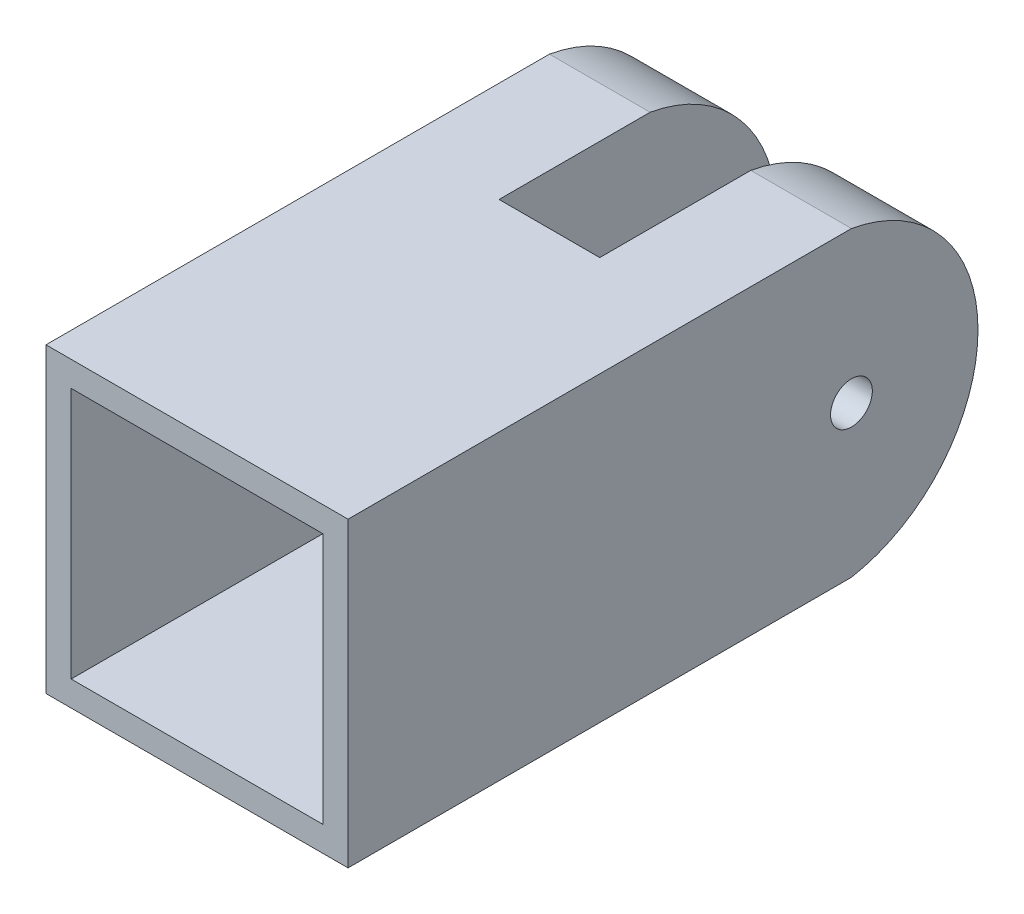
SolidWorks part; units mm, degrees
ref_plane "Front Plane" through (0, 0, 0) normal (0, 0, 1) x (1, 0, 0)
ref_plane "Top Plane" through (0, 0, 0) normal (0, 1, 0) x (1, 0, 0)
ref_plane "Right Plane" through (0, 0, 0) normal (1, 0, 0) x (0, 0, -1)
sketch "Sketch2" plane through (0, 0, 0) normal (0, 0, 1) x (1, 0, 0)
  line L1 (-30, 30) -> (30, 30)
  line L2 (-30, 30) -> (-30, -30)
  line L3 (-30, -30) -> (30, -30)
  line L4 (30, 30) -> (30, -30)
  line L5 (-30, 30) -> (30, -30) construction
  line L6 (-30, -30) -> (30, 30) construction
  point P0 (0, 0)
  dimension "D1" = 60
  dimension "D2" = 60
extrude "Boss-Extrude1" add sketch "Sketch2" along normal blind 70
ref_plane "Plane1" through (0, 0, 0) normal (0, 0, -1) x (-1, 0, 0)
sketch "Sketch3" plane through (0, 0, 0) normal (0, 0, -1) x (-1, 0, 0)
  line L0 (-30, 30) -> (30, 30) construction
  line L1 (30, -30) -> (10, -30)
  line L2 (30, -30) -> (30, 30)
  line L3 (30, 30) -> (10, 30)
  line L4 (10, -30) -> (10, 30)
  line L6 (-30, -30) -> (-10, -30)
  line L7 (-30, -30) -> (-30, 30)
  line L8 (-30, 30) -> (-10, 30)
  line L9 (-10, -30) -> (-10, 30)
  dimension "D1" = 20
  dimension "D2" = 20
extrude "Boss-Extrude2" add sketch "Sketch3" along normal blind 30
ref_plane "Plane2" through (-30, 0, 0) normal (-1, 0, 0) x (0, 0, 1)
sketch "Sketch4" plane through (-30, 0, 0) normal (-1, 0, 0) x (0, 0, 1)
  line L0 (-30, -30) -> (-30, 30)
  arc A0 (-30, -30) -> (-30, 30) centre (-24.6689, 0) cw
  dimension "D1" = 30.47
extrude "Boss-Extrude3" add sketch "Sketch4" against normal blind 20
ref_plane "Plane3" through (30, 0, 0) normal (1, 0, 0) x (0, 0, -1)
sketch "Sketch5" plane through (30, 0, 0) normal (1, 0, 0) x (0, 0, -1)
  line L0 (30, 30) -> (30, -30)
  arc A0 (30, 30) -> (30, -30) centre (24.6689, 0) cw
  dimension "D1" = 30.47
extrude "Boss-Extrude4" add sketch "Sketch5" against normal blind 20
ref_plane "Plane4" through (0, 0, 70) normal (0, 0, 1) x (1, 0, 0)
sketch "Sketch6" plane through (0, 0, 70) normal (0, 0, 1) x (1, 0, 0)
  line L0 (30, 30) -> (-30, 30) construction
  line L1 (-25, 25) -> (25, 25)
  line L2 (-25, 25) -> (-25, -25)
  line L3 (-25, -25) -> (25, -25)
  line L4 (25, 25) -> (25, -25)
  line L5 (-25, 25) -> (25, -25) construction
  line L6 (-25, -25) -> (25, 25) construction
  line L7 (30, -30) -> (30, 30) construction
  point P0 (0, 0)
  dimension "D1" = 5
  dimension "D2" = 5
extrude "Cut-Extrude1" cut sketch "Sketch6" against normal blind 67
ref_plane "Plane5" through (10, 0, 0) normal (-1, 0, 0) x (0, 0, 1)
sketch "Sketch7" plane through (10, 0, 0) normal (-1, 0, 0) x (0, 0, 1)
  line L0 (0, -30) -> (0, 30) construction
  circle A0 centre (-30, 0) radius 4.15
  dimension "D2" = 8.3
  dimension "D1" = 30
extrude "Cut-Extrude2" cut sketch "Sketch7" against normal through all
ref_plane "Plane6" through (-10, 0, 0) normal (1, 0, 0) x (0, 0, -1)
sketch "Sketch9" plane through (-10, 0, 0) normal (1, 0, 0) x (0, 0, -1)
  line L0 (0, 30) -> (0, -30) construction
  circle A0 centre (30, 0) radius 4.15
  dimension "D2" = 8.3
  dimension "D1" = 30
extrude "Cut-Extrude3" cut sketch "Sketch9" against normal through all
